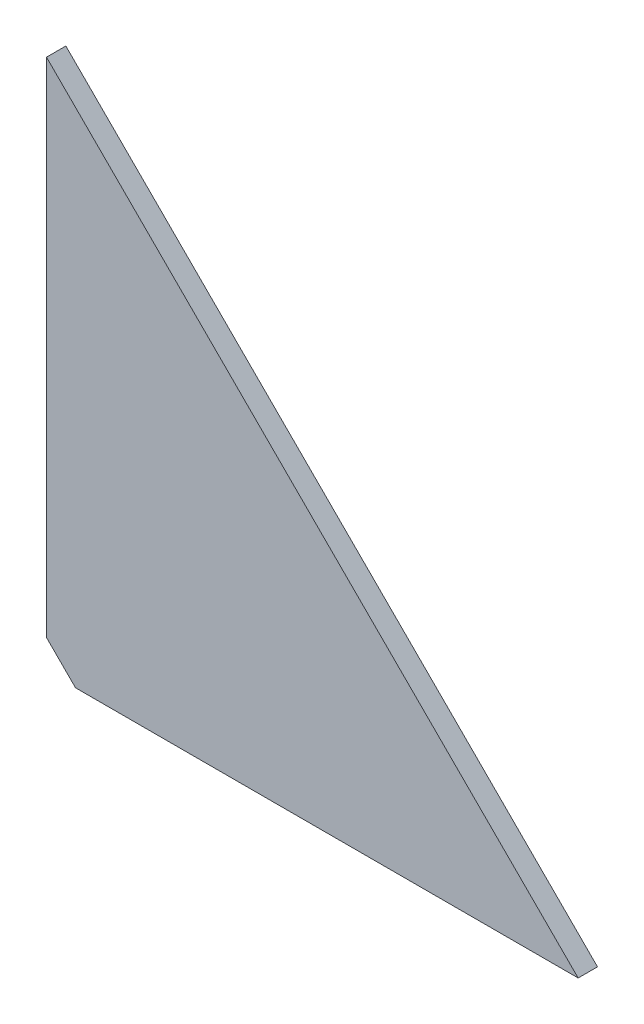
SolidWorks part; units mm, degrees
material "Простая углеродистая сталь"
ref_plane "Спереди" through (0, 0, 0) normal (0, 0, 1) x (1, 0, 0)
ref_plane "Сверху" through (0, 0, 0) normal (0, 1, 0) x (1, 0, 0)
ref_plane "Справа" through (0, 0, 0) normal (1, 0, 0) x (0, 0, -1)
sketch "Эскиз1" plane through (0, 0, 0) normal (0, 0, 1) x (1, 0, 0)
  line L0 (0, 110) -> (0, 0)
  line L1 (0, 0) -> (110, 0)
  line L2 (110, 0) -> (0, 110)
  dimension "D1" = 110
  dimension "D2" = 110
base flange "Базовая кромка1" sketch "Эскиз1" thickness 4 reverse thickness direction no parameters "D1"=1
chamfer "Фаска1" distance 6 angle 45 1 edges at (0, 0, -2)
sketch "Сгиб-Линии1" plane through (0, 0, 0) normal (0, 1, 0) x (1, 0, 0)
sketch "Граничная рамка1" plane through (0, 0, 0) normal (0, 1, 0) x (1, 0, 0)
sheet metal parameters "Листовой металл1" thickness 4 parameters "D1"=1
flat pattern "Развертка1" [suppressed]
sketch "Сгиб-Линии2" plane through (0, 0, 0) normal (0, 1, 0) x (1, 0, 0)
sketch3d "Граничная рамка2" [suppressed]
  line L0 (0, 80, 0) -> (80, 0, 0) construction
  line L1 (-38.5, 41.5, 0) -> (41.5, -38.5, 0) construction
  line L2 (0, 80, 0) -> (-38.5, 41.5, 0) construction
  line L3 (80, 0, 0) -> (41.5, -38.5, 0) construction
